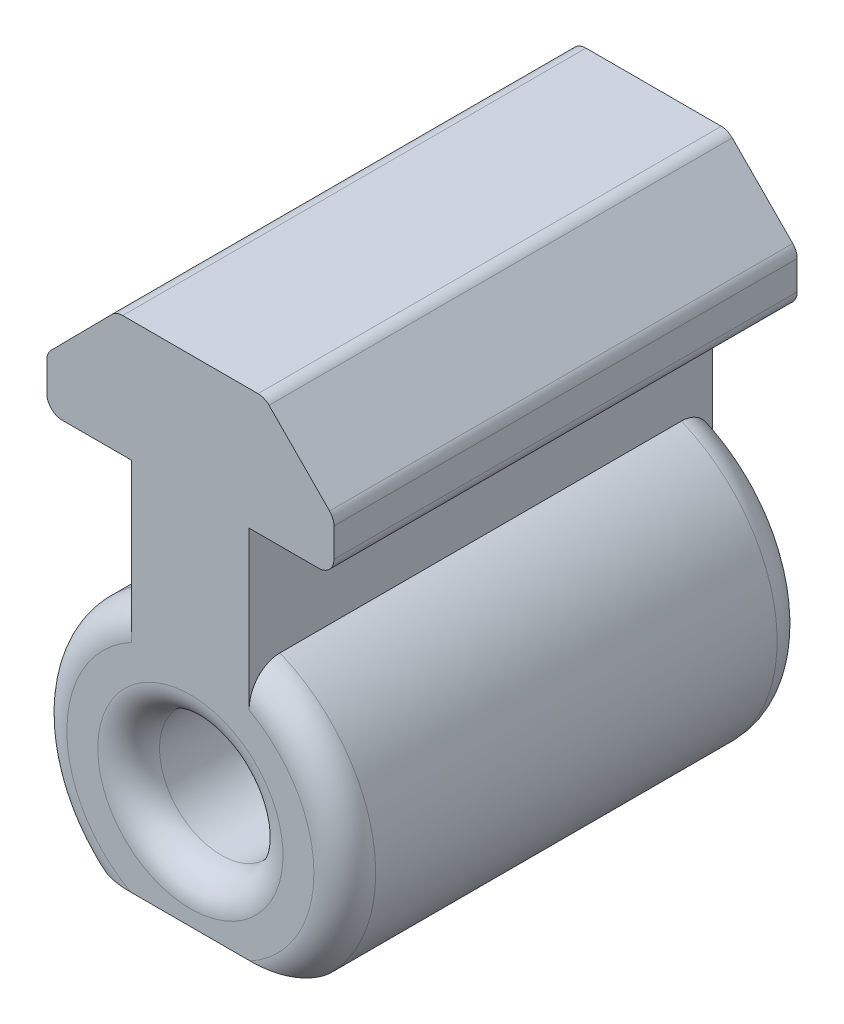
SolidWorks part; units mm, degrees
ref_plane "Front Plane" through (0, 0, 0) normal (0, 0, 1) x (1, 0, 0)
ref_plane "Top Plane" through (0, 0, 0) normal (0, 1, 0) x (1, 0, 0)
ref_plane "Right Plane" through (0, 0, 0) normal (1, 0, 0) x (0, 0, -1)
sketch "Sketch1" plane through (0, 0, 0) normal (0, 0, 1) x (1, 0, 0)
  line L0 (0, 0) -> (0, 44.9793) construction
  line L5 (3.8, 0) -> (-3.8, 0)
  line L6 (-3.8, 0) -> (-3.8, 8)
  line L7 (-3.8, 8) -> (-9.3, 8)
  line L8 (-9.3, 8) -> (-9.3, 11.28)
  line L9 (-9.3, 11.28) -> (-4.8, 15.8308)
  line L10 (-4.8, 15.8308) -> (4.8, 15.8308)
  line L11 (0, 15.8308) -> (0, 0) construction
  line L12 (9.3, 11.28) -> (4.8, 15.8308)
  line L13 (9.3, 8) -> (9.3, 11.28)
  line L14 (3.8, 8) -> (9.3, 8)
  line L15 (3.8, 0) -> (3.8, 8)
  dimension "D1" = 3.8
  dimension "D2" = 8
  dimension "D3" = 5.5
  dimension "D4" = 3.28
  dimension "D5" = 6.4
  dimension "D6" = 4.8
extrude "Boss-Extrude1" add sketch "Sketch1" along normal blind 30
fillet "Fillet1" radius 1 6 edges at (9.3, 8, 15) (-9.3, 8, 15) (-9.3, 11.28, 15) (9.3, 11.28, 15) (-4.8, 15.8308, 15) (4.8, 15.8308, 15)
sketch "Sketch3" plane through (0, 0, 0) normal (0, 0, -1) x (-1, 0, 0)
  line L0 (0, 0) -> (0, -50000) construction
  circle A0 centre (0, -9.2499) radius 4
  circle A1 centre (0, -9.2499) radius 10
  dimension "D1" = 20
  dimension "D2" = 8
extrude "Boss-Extrude2" add sketch "Sketch3" against normal up to surface (30 mm away) up to face at (0, 9.8373, 30)
sketch "Sketch5" plane through (0, 0, 0) normal (0, 0, 1) x (1, 0, 0)
  line L0 (-7.1414, -16.2499) -> (7.1414, -16.2499)
  circle A0 centre (0, -9.2499) radius 10
  arc A1 (-3.8, 0) -> (3.8, 0) centre (0, -9.2499) ccw construction
  dimension "D1" = 7
extrude "Cut-Extrude1" cut sketch "Sketch5" along normal through all contours L0 A0 region at (0, -17.4668, 0)
fillet "Fillet2" radius 2 6 edges at (-9.7951, -7.2357, 0) (9.7951, -7.2357, 0) (-9.7951, -7.2357, 30) (9.7951, -7.2357, 30) (-4, -9.2499, 30) (-4, -9.2499, 0)
